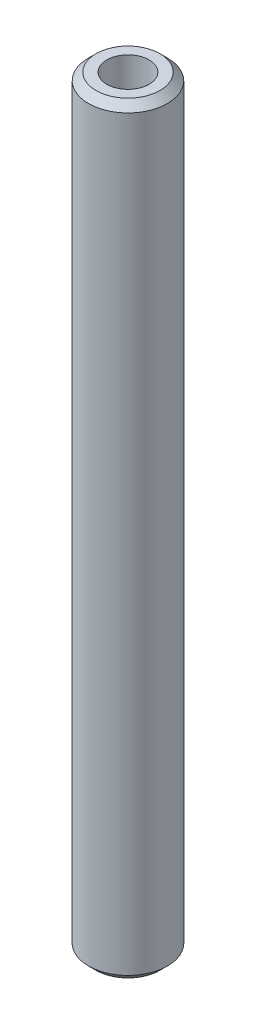
SolidWorks part; units mm, degrees
ref_plane "Front Plane" through (0, 0, 0) normal (0, 0, 1) x (1, 0, 0)
ref_plane "Top Plane" through (0, 0, 0) normal (0, 1, 0) x (1, 0, 0)
ref_plane "Right Plane" through (0, 0, 0) normal (1, 0, 0) x (0, 0, -1)
sketch "Sketch1" plane through (0, 0, 0) normal (0, 1, 0) x (1, 0, 0)
  circle A0 centre (0, 0) radius 27.5
  dimension "SHAFT_OD" = 55
extrude "Boss-Extrude1" add sketch "Sketch1" along normal blind 530.9015
sketch "Sketch2" plane through (0, 0, 0) normal (0, 1, 0) x (1, 0, 0)
  circle A0 centre (0, 0) radius 14.7454
  dimension "BORE_D" = 29.4908
extrude "Cut-Extrude1" cut sketch "Sketch2" along normal through all
chamfer "Chamfer1" distance 5.2359 angle 45 2 edges at (0, 530.9015, 27.5) (0, 0, 27.5)
